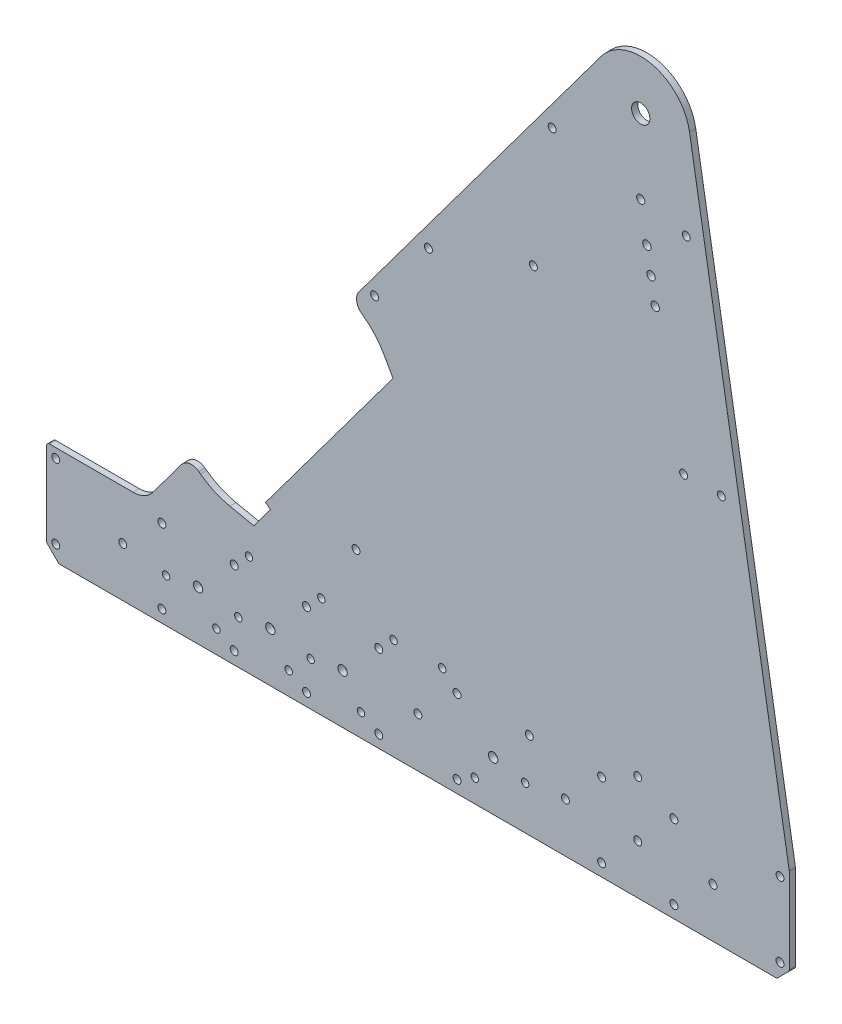
SolidWorks part; units mm, degrees
ref_plane "Front Plane" through (0, 0, 0) normal (0, 0, 1) x (1, 0, 0)
ref_plane "Top Plane" through (0, 0, 0) normal (0, 1, 0) x (1, 0, 0)
ref_plane "Right Plane" through (0, 0, 0) normal (1, 0, 0) x (0, 0, -1)
sketch "Sketch1" plane through (0, 0, 0) normal (0, 0, 1) x (1, 0, 0)
  line L1 (0, 0) -> (381, 0)
  line L2 (0, 0) -> (0, 50.8)
  line L4 (381, 0) -> (381, 50.8)
  line L5 (381, 50.8) -> (329.8448, 353.4827)
  line L6 (0, 50.8) -> (44.4242, 50.8)
  line L7 (54.6089, 55.913) -> (73.025, 80.6347)
  line L9 (112.3289, 80.2488) -> (177.7421, 168.0591)
  line L11 (156.4817, 192.6662) -> (284.4306, 364.4239)
  line L12 (112.3289, 80.2488) -> (114.875, 78.3521)
  line L13 (114.875, 78.3521) -> (106.3397, 66.8943)
  line L14 (156.4817, 192.6662) -> (169.2125, 183.1825)
  line L15 (169.2125, 183.1825) -> (177.7421, 168.0591)
  line L16 (73.025, 80.6347) -> (85.7559, 71.151)
  line L17 (85.7559, 71.151) -> (106.3397, 66.8943)
  line L18 (169.2125, 183.1825) -> (85.7559, 71.151) construction
  arc A0 (284.4306, 364.4239) -> (329.8448, 353.4827) centre (304.8, 349.25) cw
  arc A1 (44.4242, 50.8) -> (54.6089, 55.913) centre (44.4242, 63.5) ccw
  point P11 (50.8, 50.8)
  dimension "D4" = 349.25
  dimension "D7" = 12.7
  dimension "D5" = 25.4
  dimension "D1" = 50.8
  dimension "D2" = 381
  dimension "D3" = 76.2
  dimension "D6" = 50.8
  dimension "D8" = 123.825
  dimension "D9" = 139.7
  dimension "D10" = 15.875
  dimension "D11" = 31.75
  dimension "D12" = 73.025
  dimension "D13" = 3.175
  dimension "D14" = 14.2875
  dimension "D15" = 115
extrude "Boss-Extrude1" add sketch "Sketch1" along normal blind 3.175
sketch "Sketch2" plane through (0, 0, 3.175) normal (0, 0, 1) x (1, 0, 0)
  line L1 (190.5, 50.8) -> (190.5, 0) construction
  line L3 (0, 0) -> (381, 0) construction
  line L5 (0, 6.35) -> (0, 0)
  line L6 (0, 50.8) -> (0, 0) construction
  line L7 (0, 0) -> (6.35, 0)
  line L8 (6.35, 0) -> (0, 6.35)
  line L9 (381, 0) -> (374.65, 0)
  line L10 (374.65, 0) -> (381, 6.35)
  line L11 (381, 6.35) -> (381, 0)
  circle A19 centre (4.7625, 46.0375) radius 2.032
  circle A20 centre (4.7625, 7.9375) radius 2.032
  circle A21 centre (376.2375, 7.9375) radius 2.032
  circle A22 centre (376.2375, 46.0375) radius 2.032
  dimension "D21" = 6.35
  dimension "D27" = 4.064
  dimension "D4" = 46.0375
  dimension "D22" = 6.35
  dimension "D25" = 4.7625
  dimension "D28" = 7.9375
extrude "Cut-Extrude1" cut sketch "Sketch2" against normal up to next
sketch "Sketch5" plane through (0, 0, 3.175) normal (0, 0, 1) x (1, 0, 0)
  line L0 (151.892, 25.4) -> (229.108, 25.4) construction
  line L1 (229.108, 25.4) -> (341.884, 25.4) construction
  circle A0 centre (39.116, 25.4) radius 2.032
  circle A1 centre (59.182, 6.35) radius 2.032
  circle A2 centre (59.182, 44.45) radius 2.032
  circle A3 centre (96.266, 44.45) radius 2.032
  circle A4 centre (133.35, 44.45) radius 2.032
  circle A5 centre (170.434, 44.45) radius 2.032
  circle A6 centre (210.566, 44.45) radius 2.032
  circle A7 centre (210.566, 6.35) radius 2.032
  circle A8 centre (170.434, 6.35) radius 2.032
  circle A9 centre (247.65, 44.45) radius 2.032
  circle A10 centre (266.192, 25.4) radius 2.032
  circle A11 centre (39.116, 25.4) radius 2.286 construction
  circle A12 centre (59.182, 44.45) radius 1.905 construction
  circle A13 centre (59.182, 6.35) radius 1.905 construction
  circle A14 centre (96.266, 44.45) radius 1.905 construction
  circle A15 centre (133.35, 44.45) radius 1.905 construction
  circle A16 centre (170.434, 44.45) radius 1.905 construction
  circle A17 centre (170.434, 6.35) radius 2.159 construction
  circle A18 centre (210.566, 6.35) radius 2.159 construction
  circle A19 centre (210.566, 44.45) radius 1.905 construction
  circle A20 centre (247.65, 44.45) radius 1.905 construction
  circle A21 centre (266.192, 25.4) radius 2.286 construction
  circle A22 centre (77.724, 25.4) radius 2.3813
  circle A23 centre (114.808, 25.4) radius 2.3813
  circle A24 centre (151.892, 25.4) radius 2.3813
  circle A25 centre (229.108, 25.4) radius 2.3813
  circle A26 centre (190.5, 25.4) radius 2.032
  circle A28 centre (303.276, 25.4) radius 2.032
  circle A29 centre (341.884, 25.4) radius 2.032
  circle A30 centre (77.724, 25.4) radius 7.366 construction
  circle A31 centre (114.808, 25.4) radius 7.366 construction
  circle A32 centre (151.892, 25.4) radius 7.366 construction
  circle A33 centre (229.108, 25.4) radius 7.366 construction
  dimension "D1" = 4.064
  dimension "D2" = 4.7625
  dimension "D3" = 37.084
  dimension "D4" = 38.608
  dimension "D5" = 38.608
extrude "Cut-Extrude4" cut sketch "Sketch5" against normal through all
sketch "Sketch6" plane through (0, 0, 3.175) normal (0, 0, 1) x (1, 0, 0)
  line L0 (6.35, 0) -> (374.65, 0) construction
  line L1 (266.192, 25.4) -> (303.276, 25.4) construction
  line L2 (284.734, 6.35) -> (284.734, 44.45) construction
  line L3 (151.892, 25.4) -> (114.808, 25.4) construction
  line L4 (114.808, 25.4) -> (77.724, 25.4) construction
  circle A0 centre (284.734, 44.45) radius 2.032
  circle A1 centre (284.734, 6.35) radius 2.032
  circle A2 centre (321.818, 6.35) radius 2.032
  circle A3 centre (321.818, 44.45) radius 2.032
  circle A4 centre (96.266, 6.35) radius 2.032
  circle A5 centre (133.35, 6.35) radius 2.032
  circle A6 centre (303.276, 53.975) radius 2.032
  arc A7 (304.329, 52.3875) -> (302.223, 52.3875) centre (303.276, 53.975) ccw construction
  point P8 (284.734, 25.4)
  point P9 (284.734, 25.4)
  point P28 (96.266, 25.4)
  point P30 (133.35, 25.4)
  dimension "D1" = 4.064
  dimension "D2" = 6.35
  dimension "D3" = 37.084
extrude "Cut-Extrude5" cut sketch "Sketch6" against normal through all
sketch "Sketch3" plane through (0, 0, 3.175) normal (0, 0, 1) x (1, 0, 0)
  line L0 (73.025, 80.6347) -> (54.6089, 55.913) construction
  line L1 (381, 6.35) -> (381, 50.8) construction
  line L2 (6.35, 0) -> (374.65, 0) construction
  line L3 (304.8, 349.25) -> (304.8, 311.15) construction
  line L4 (307.9745, 292.3664) -> (304.8, 311.15) construction
  line L5 (307.9745, 292.3664) -> (310.0909, 279.8439) construction
  line L6 (310.0909, 279.8439) -> (312.2073, 267.3215) construction
  line L7 (381, 50.8) -> (329.8448, 353.4827) construction
  line L8 (73.025, 80.6347) -> (54.6089, 55.913) construction
  line L9 (0, 50.8) -> (0, 6.35) construction
  circle A0 centre (304.8, 349.25) radius 4.699
  circle A1 centre (168.275, 200.025) radius 2.032
  circle A2 centre (158.75, 82.55) radius 2.032
  circle A3 centre (304.8, 311.15) radius 2.0955
  circle A5 centre (307.9745, 292.3664) radius 2.159
  circle A6 centre (310.0909, 279.8439) radius 2.159
  circle A7 centre (312.2073, 267.3215) radius 2.159
  circle A8 centre (328.1309, 306.4656) radius 2.032
  circle A9 centre (346.12, 200.025) radius 2.032
  circle A10 centre (195.8987, 234.95) radius 2.032
  circle A11 centre (249.7483, 254.0902) radius 2.032
  circle A12 centre (259.3534, 320.1311) radius 2.032
  circle A13 centre (326.7999, 200.025) radius 2.032
  dimension "D1" = 9.398
  dimension "D3" = 4.064
  dimension "D6" = 4.064
  dimension "D11" = 4.318
  dimension "D10" = 4.191
  dimension "D13" = 4.064
  dimension "D20" = 4.064
  dimension "D4" = 222.25
  dimension "D5" = 82.55
  dimension "D7" = 19.05
  dimension "D8" = 12.7
  dimension "D9" = 38.1
  dimension "D12" = 12.7
  dimension "D14" = 9.525
  dimension "D15" = 9.525
  dimension "D16" = 107.95
  dimension "D17" = 200.025
  dimension "D18" = 6.35
  dimension "D19" = 234.95
  dimension "D21" = 57.15
  dimension "D22" = 38.1
  dimension "D23" = 53.975
  dimension "D24" = 6.35
  dimension "D25" = 200.025
  dimension "D26" = 168.275
  dimension "D27" = 28.575
extrude "Cut-Extrude2" cut sketch "Sketch3" against normal through all
fillet "Fillet1" radius 1.5875 6 edges at (374.65, 0, 1.5875) (381, 6.35, 1.5875) (381, 50.8, 1.5875) (6.35, 0, 1.5875) (0, 6.35, 1.5875) (0, 50.8, 1.5875)
sketch "Sketch4" plane through (0, 0, 0) normal (0, 0, -1) x (-1, 0, 0)
  circle A0 centre (-61.3181, 22.2981) radius 1.905 construction
  circle A1 centre (-87.1313, 11.606) radius 1.905 construction
  circle A2 centre (-98.4021, 22.2981) radius 1.905 construction
  circle A3 centre (-124.2153, 11.606) radius 1.905 construction
  circle A4 centre (-135.4861, 22.2981) radius 1.905 construction
  circle A5 centre (-161.2993, 11.606) radius 1.905 construction
  circle A6 centre (-245.5139, 22.2981) radius 1.905 construction
  circle A7 centre (-219.7007, 11.606) radius 1.905 construction
  circle A8 centre (-202.982, 51.9684) radius 1.905 construction
  circle A9 centre (-178.018, 51.9684) radius 1.905 construction
  circle A10 centre (-140.934, 51.9684) radius 1.905 construction
  circle A11 centre (-103.85, 51.9684) radius 1.905 construction
  circle A12 centre (-61.3181, 22.2981) radius 1.905
  circle A13 centre (-87.1313, 11.606) radius 1.905
  circle A14 centre (-98.4021, 22.2981) radius 1.905
  circle A15 centre (-124.2153, 11.606) radius 1.905
  circle A16 centre (-135.4861, 22.2981) radius 1.905
  circle A17 centre (-161.2993, 11.606) radius 1.905
  circle A18 centre (-245.5139, 22.2981) radius 1.905
  circle A19 centre (-219.7007, 11.606) radius 1.905
  circle A20 centre (-202.982, 51.9684) radius 1.905
  circle A21 centre (-178.018, 51.9684) radius 1.905
  circle A22 centre (-140.934, 51.9684) radius 1.905
  circle A23 centre (-103.85, 51.9684) radius 1.905
extrude "Cut-Extrude3" cut sketch "Sketch4" against normal up to next
fillet "Fillet2" radius 38.1 2 edges at (85.7559, 71.151, 1.5875) (169.2125, 183.1825, 1.5875)
fillet "Fillet3" radius 6.35 2 edges at (73.025, 80.6347, 1.5875) (156.4817, 192.6662, 1.5875)
